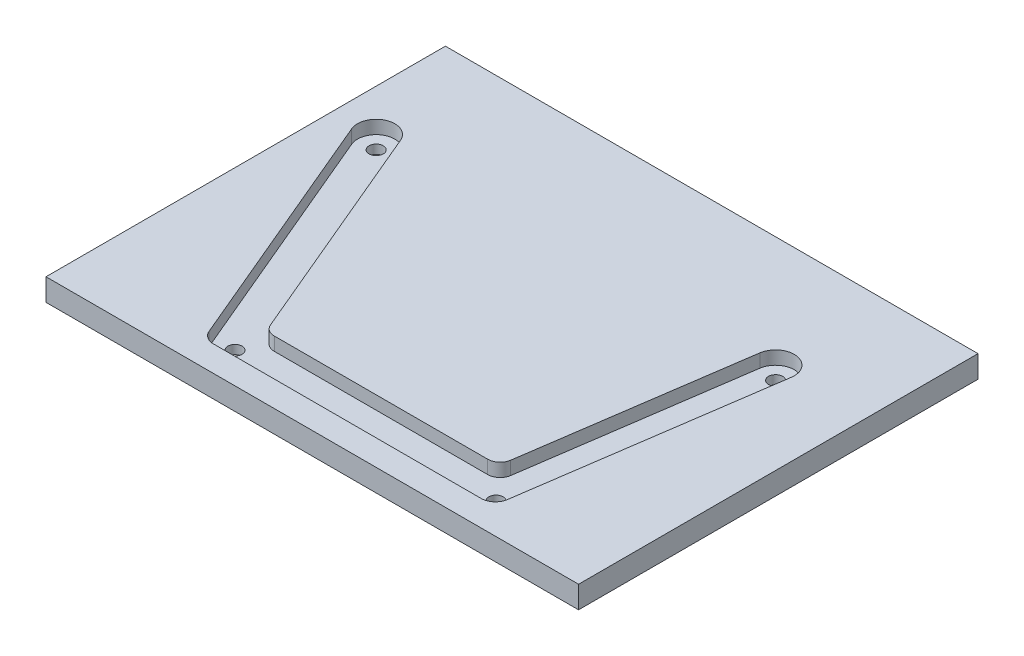
SolidWorks part; units mm, degrees
ref_plane "Front Plane" through (0, 0, 0) normal (0, 0, 1) x (1, 0, 0)
ref_plane "Top Plane" through (0, 0, 0) normal (0, 1, 0) x (1, 0, 0)
ref_plane "Right Plane" through (0, 0, 0) normal (1, 0, 0) x (0, 0, -1)
sketch "Sketch1" plane through (0, 0, 0) normal (0, 1, 0) x (1, 0, 0)
  line L1 (-60, 45) -> (60, 45)
  line L2 (-60, 45) -> (-60, -45)
  line L3 (-60, -45) -> (60, -45)
  line L4 (60, 45) -> (60, -45)
  point P4 (-60, 0)
  point P6 (0, -45)
  dimension "D1" = 120
  dimension "D2" = 90
extrude "Boss-Extrude1" add sketch "Sketch1" along normal blind 5
sketch "Sketch2" plane through (0, 5, 0) normal (0, 1, 0) x (1, 0, 0)
  point P38 (0, 0)
  point P39 (0, 0)
  line B0 (-50.5697, 19.9611) -> (-27.3697, -35.0389) construction
  line B1 (-27.3697, -35.0389) -> (31.4303, -35.0389) construction
  line B2 (39.4303, 19.9611) -> (31.4303, -35.0389) construction
  line B3 (-54.2553, 18.4065) -> (-30.7974, -37.2049) construction
  line B4 (-28.0332, -39.0389) -> (32.2953, -39.0389) construction
  line B5 (43.3886, 19.3853) -> (35.2641, -36.4707) construction
  line B6 (-46.8842, 21.5157) -> (-25.4893, -29.2049) construction
  line B7 (-22.7252, -31.0389) -> (25.3748, -31.0389) construction
  line B8 (35.4719, 20.5369) -> (28.3435, -28.4707) construction
  line B9 (-54.4395, 18.3287) -> (-30.9817, -37.2826)
  line B10 (-28.0332, -39.2389) -> (32.2953, -39.2389)
  line B11 (43.5865, 19.3565) -> (35.462, -36.4995)
  line B12 (35.274, 20.5656) -> (28.1456, -28.4419)
  line B13 (-22.7252, -30.8389) -> (25.3748, -30.8389)
  line B14 (-46.6999, 21.5934) -> (-25.3051, -29.1271)
  arc B15 (-54.2553, 18.4065) -> (-46.8842, 21.5157) centre (-50.5697, 19.9611) cw construction
  arc B16 (43.3886, 19.3853) -> (35.4719, 20.5369) centre (39.4303, 19.9611) ccw construction
  arc B17 (25.3748, -31.0389) -> (28.3435, -28.4707) centre (25.3748, -28.0389) ccw construction
  arc B18 (32.2953, -39.0389) -> (35.2641, -36.4707) centre (32.2953, -36.0389) ccw construction
  arc B19 (-28.0332, -39.0389) -> (-30.7974, -37.2049) centre (-28.0332, -36.0389) cw construction
  arc B20 (-22.7252, -31.0389) -> (-25.4893, -29.2049) centre (-22.7252, -28.0389) cw construction
  arc B21 (-28.0332, -39.2389) -> (-30.9817, -37.2826) centre (-28.0332, -36.0389) cw
  arc B22 (32.2953, -39.2389) -> (35.462, -36.4995) centre (32.2953, -36.0389) ccw
  arc B23 (43.5865, 19.3565) -> (35.274, 20.5656) centre (39.4303, 19.9611) ccw
  arc B24 (25.3748, -30.8389) -> (28.1456, -28.4419) centre (25.3748, -28.0389) ccw
  arc B25 (-22.7252, -30.8389) -> (-25.3051, -29.1271) centre (-22.7252, -28.0389) cw
  arc B26 (-54.4395, 18.3287) -> (-46.6999, 21.5934) centre (-50.5697, 19.9611) cw
sketch_block_instance "Block1-1"
sketch_block "Block1"
extrude "Cut-Extrude2" cut sketch "Sketch2" against normal blind 3
sketch "Sketch3" plane through (0, 2, 0) normal (0, 1, 0) x (1, 0, 0)
  line L0 (39.4303, 19.9611) -> (31.4303, -35.0389) construction
  line L1 (-27.3697, -35.0389) -> (31.4303, -35.0389) construction
  line L2 (-50.5697, 19.9611) -> (-27.3697, -35.0389) construction
  line L3 (39.4303, 19.9611) -> (31.4303, -35.0389)
  line L4 (-27.3697, -35.0389) -> (31.4303, -35.0389)
  line L5 (-50.5697, 19.9611) -> (-27.3697, -35.0389)
  circle A0 centre (-50.5697, 19.9611) radius 1.6
  circle A1 centre (-27.3697, -35.0389) radius 1.6
  circle A2 centre (31.4303, -35.0389) radius 1.6
  circle A4 centre (39.4303, 19.9611) radius 1.6
  dimension "D1" = 3.2
  dimension "D2" = 3.2
  dimension "D3" = 3.2
  dimension "D4" = 3.2
extrude "Cut-Extrude3" cut sketch "Sketch3" against normal through all contours A0 | A1 | A2 | A4
sketch "Sketch4" plane through (0, 5, 0) normal (0, 1, 0) x (1, 0, 0)
  line L0 (-3.5897, -14.7859) -> (12.4103, -14.7859)
  arc A0 (12.4103, -14.7859) -> (-3.5897, -14.7859) centre (4.4103, 9.3214) ccw
  circle A1 centre (-27.3697, -35.0389) radius 1.6 construction
  point P4 (0, 0)
  point P5 (0, 0)
  dimension "D2" = 50.8
  dimension "D4" = 20.253
  dimension "D1" = 16
  dimension "D3" = 23.78
